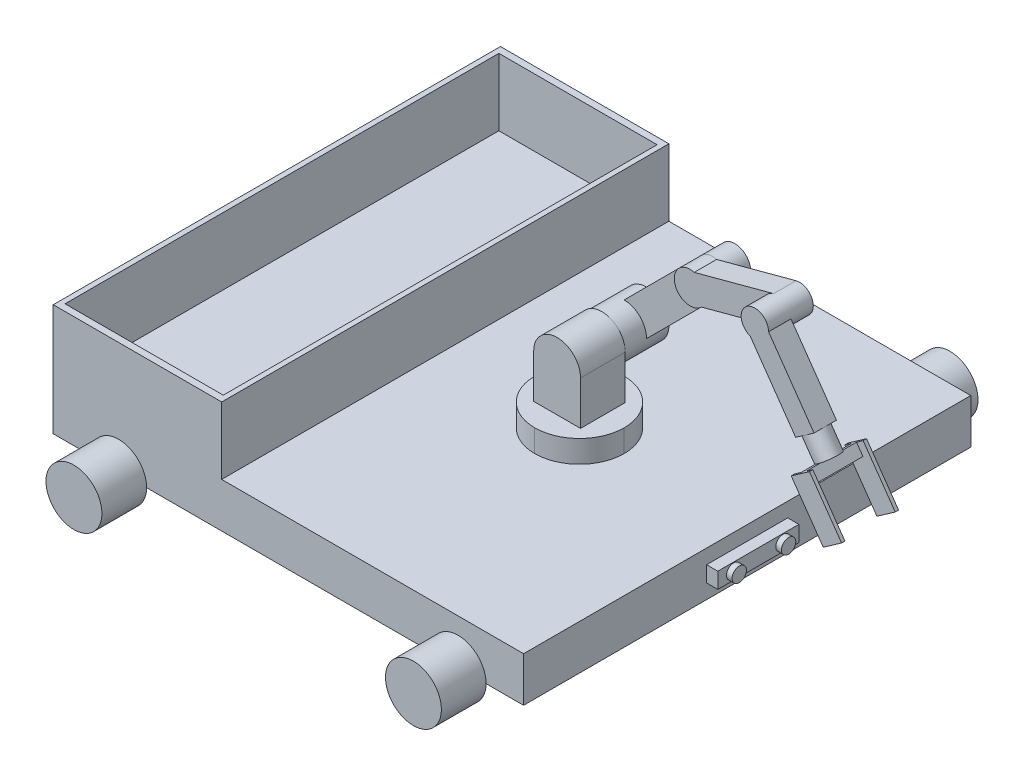
SolidWorks part; units mm, degrees
ref_plane "Front Plane" through (0, 0, 0) normal (0, 0, 1) x (1, 0, 0)
ref_plane "Top Plane" through (0, 0, 0) normal (0, 1, 0) x (1, 0, 0)
ref_plane "Right Plane" through (0, 0, 0) normal (1, 0, 0) x (0, 0, -1)
sketch "Sketch1" plane through (0, 0, 0) normal (0, 0, 1) x (1, 0, 0)
  line L0 (0, 0) -> (0, 4) construction
  line L1 (0, 0) -> (60, 0)
  line L2 (0, 4) -> (60, 4)
  line L3 (60, 4) -> (60, 0)
  line L4 (0, 4) -> (0, 0)
  line L5 (5.8519, 4) -> (5.8519, 0) construction
  line L6 (30, 4) -> (30, 0) construction
  line L7 (54.1481, 4) -> (54.1481, 0) construction
  dimension "D1" = 4
  dimension "D2" = 5.8519
extrude "Boss-Extrude1" add sketch "Sketch1" along normal blind 40
sketch "Sketch2" plane through (0, 0, 40) normal (0, 0, 1) x (1, 0, 0)
  circle A0 centre (5.8519, 0) radius 2.5
  circle A1 centre (54.1481, 0) radius 2.5
extrude "Boss-Extrude2" add sketch "Sketch2" along normal blind 4
sketch "Sketch3" plane through (0, 0, 40) normal (0, 0, 1) x (1, 0, 0)
  circle A0 centre (54.1481, 0) radius 2.5 construction
  circle A1 centre (5.8519, 0) radius 2.5 construction
  circle A2 centre (54.1481, 0) radius 2.5
  circle A3 centre (5.8519, 0) radius 2.5
extrude "Boss-Extrude3" add sketch "Sketch3" against normal blind 4 from offset 40 offset against normal yes
sketch "Sketch4" plane through (0, 0, 0) normal (0, 0, -1) x (-1, 0, 0)
  line L0 (-60, 2) -> (-30, 2) construction
  line L1 (-60, 4) -> (-60, 0) construction
  line L2 (-30, 4) -> (-30, 0) construction
  line L3 (-30, 4) -> (-45, 4) construction
  line L4 (0, 4) -> (-60, 4) construction
  line L5 (-45, 4) -> (-45, 6) construction
  line L6 (-45, 6) -> (-41, 6)
  line L7 (-41, 6) -> (-41, 4)
  line L8 (-41, 4) -> (-49, 4)
  line L9 (-49, 4) -> (-49, 6)
  line L10 (-49, 6) -> (-45, 6)
  dimension "D1" = 15
  dimension "D2" = 2
extrude "Boss-Extrude4" add sketch "Sketch4" along normal blind 4 and the other way blind 4 from offset 20 offset against normal yes
fillet "Fillet1" radius 4 4 edges at (49, 5, 24) (41, 5, 24) (41, 5, 16) (49, 5, 16)
sketch "Sketch5" plane through (0, 6, 0) normal (0, 1, 0) x (1, 0, 0)
  line L0 (45, -16) -> (45, -24) construction
  line L2 (42.906, -18) -> (47.094, -18)
  line L3 (42.906, -18) -> (42.906, -22)
  line L4 (42.906, -22) -> (47.094, -22)
  line L5 (47.094, -18) -> (47.094, -22)
  line L6 (42.906, -18) -> (47.094, -22) construction
  line L7 (42.906, -22) -> (47.094, -18) construction
  point P4 (45, -20)
  dimension "D1" = 4
extrude "Boss-Extrude5" add sketch "Sketch5" along normal blind 6
fillet "Fillet2" 2 edges at (47.094, 12, 20) (42.906, 12, 20) type full round first side face at (47.094, 9, 20) second side face at (42.906, 9, 20) middle face at (45, 12, 20)
sketch "Sketch6" plane through (0, 0, 18) normal (0, 0, -1) x (-1, 0, 0)
  line L0 (-47.094, 9.906) -> (-42.906, 9.906) construction
  circle A0 centre (-45, 9.906) radius 2
extrude "Boss-Extrude6" add sketch "Sketch6" along normal blind 2
sketch "Sketch7" plane through (0, 0, 16) normal (0, 0, -1) x (-1, 0, 0)
  line L0 (-47, 9.906) -> (-54.8995, 17.8055)
  line L1 (-45, 11.906) -> (-45, 7.906) construction
  line L2 (-54.8995, 17.8055) -> (-52.8972, 19.8077)
  line L3 (-52.8972, 19.8077) -> (-45, 11.906)
  circle A1 centre (-45, 9.906) radius 2
  arc A2 (-47, 9.906) -> (-45, 11.906) centre (-45, 9.906) ccw
  dimension "D2" = 45
  dimension "D1" = 0
extrude "Boss-Extrude7" add sketch "Sketch7" along normal blind 2
fillet "Fillet3" 2 edges at (54.8995, 17.8055, 15) (52.8972, 19.8077, 15) type full round first side face at (50.9497, 13.8557, 15) second side face at (48.9486, 15.8568, 15) middle face at (53.8984, 18.8066, 15)
sketch "Sketch8" plane through (0, 0, 16) normal (0, 0, 1) x (1, 0, 0)
  line L0 (51.8962, 18.8062) -> (53.8985, 16.8045) construction
  line L1 (53.8985, 16.8045) -> (62.1901, 19.0275)
  line L2 (53.2636, 19.1727) -> (61.5551, 21.3957)
  line L4 (61.5551, 21.3957) -> (62.1901, 19.0275)
  arc A0 (53.2636, 19.1727) -> (53.8985, 16.8045) centre (52.8974, 17.8053) ccw
  dimension "D1" = 120
  dimension "D2" = 120
extrude "Boss-Extrude8" add sketch "Sketch8" along normal blind 2
fillet "Fillet5" 2 edges at (61.5551, 21.3957, 17) (62.1901, 19.0275, 17) type full round first side face at (56.5803, 20.062, 16.8) second side face at (58.0443, 17.916, 17) middle face at (61.8726, 20.2116, 17)
sketch "Sketch9" plane through (0, 0, 18) normal (0, 0, 1) x (1, 0, 0)
  line L0 (59.4625, 19.8941) -> (61.9144, 19.8941) construction
  line L1 (61.9144, 19.8941) -> (65.9832, 14.0834)
  line L2 (60.2692, 18.7421) -> (64.3379, 12.9313)
  line L3 (64.3379, 12.9313) -> (65.9832, 14.0834)
  arc A0 (61.9144, 19.8941) -> (60.2692, 18.7421) centre (60.6885, 19.8941) ccw
  dimension "D1" = 125
  dimension "D2" = 55
extrude "Boss-Extrude9" add sketch "Sketch9" along normal blind 2
sketch "Sketch10" plane through (15.0908, -21.5519, 0) normal (0.5736, -0.8192, 0) x (-0.8192, -0.5736, 0)
  line L0 (-60.1196, -19) -> (-62.1281, -19) construction
  line L1 (-60.1196, -20) -> (-60.1196, -18) construction
  line L2 (-62.1281, -20) -> (-62.1281, -18) construction
  circle A0 centre (-61.1239, -19) radius 1
extrude "Boss-Extrude10" add sketch "Sketch10" along normal blind 2
sketch "Sketch11" plane through (16.2379, -23.1902, 0) normal (0.5736, -0.8192, 0) x (0.8192, 0.5736, 0)
  line L0 (61.1239, 20) -> (61.1239, 18) construction
  line L2 (60.8513, 21.25) -> (61.3964, 21.25)
  line L3 (60.8513, 21.25) -> (60.8513, 16.75)
  line L4 (60.8513, 16.75) -> (61.3964, 16.75)
  line L5 (61.3964, 21.25) -> (61.3964, 16.75)
  line L6 (60.8513, 21.25) -> (61.3964, 16.75) construction
  line L7 (60.8513, 16.75) -> (61.3964, 21.25) construction
  circle A0 centre (61.1239, 19) radius 1 construction
  point P6 (61.1239, 19)
  dimension "D1" = 4.5
extrude "Boss-Extrude11" add sketch "Sketch11" along normal blind 1
sketch "Sketch12" plane through (16.8115, -24.0093, 0) normal (0.5736, -0.8192, 0) x (0.8192, 0.5736, 0)
  line L0 (60.1239, 21.25) -> (62.1239, 21.25)
  line L1 (61.3964, 21.25) -> (60.8513, 21.25) construction
  line L2 (61.1239, 21.25) -> (61.1239, 22.1675) construction
  line L3 (60.1239, 21.25) -> (60.1239, 21.55)
  line L4 (60.1239, 21.55) -> (62.1239, 21.55)
  line L5 (62.1239, 21.55) -> (62.1239, 21.25)
  line L6 (60.8513, 19) -> (63.7554, 19) construction
  line L7 (60.8513, 21.25) -> (60.8513, 16.75) construction
  line L8 (60.1239, 16.45) -> (62.1239, 16.45)
  line L9 (60.1239, 16.75) -> (60.1239, 16.45)
  line L10 (60.1239, 16.75) -> (62.1239, 16.75)
  line L11 (62.1239, 16.45) -> (62.1239, 16.75)
  dimension "D1" = 1
extrude "Boss-Extrude12" add sketch "Sketch12" along normal blind 4 and the other way blind 1
sketch "Sketch14" plane through (0, 0, 0) normal (0, 0, -1) x (-1, 0, 0)
  line L0 (-17.9301, 4) -> (-17.9301, 0)
  line L1 (0, 4) -> (-60, 4) construction
  line L2 (0, 0) -> (-60, 0) construction
  line L3 (-17.9301, 0) -> (-15.6133, -10.9445)
  line L4 (-15.6133, -10.9445) -> (7.529, -7.9753)
  line L5 (7.529, -7.9753) -> (13.2054, 7.6567)
  line L6 (13.2054, 7.6567) -> (12.2964, 9.6021)
  line L7 (4.9964, 18.3108) -> (-17.9301, 4)
  line L8 (4.9964, 18.3108) -> (12.2964, 9.6021)
extrude "Cut-Extrude1" cut sketch "Sketch14" against normal blind 49 and the other way blind 14
sketch "Sketch15" plane through (0, 0, 0) normal (0, 0, -1) x (-1, 0, 0)
  circle A0 centre (-23.782, 0) radius 2.5
extrude "Boss-Extrude13" add sketch "Sketch15" along normal blind 4
sketch "Sketch16" plane through (0, 0, 40) normal (0, 0, 1) x (1, 0, 0)
  circle A0 centre (23.782, 0) radius 2.5
extrude "Boss-Extrude14" add sketch "Sketch16" along normal blind 4
sketch "Sketch17" plane through (0, 4, 0) normal (0, 1, 0) x (1, 0, 0)
  line L0 (17.9301, 0) -> (17.9301, -40) construction
  line L1 (17.9301, 0) -> (17.9301, -40)
  line L2 (32.9972, 0) -> (32.9972, -40)
  line L3 (60, 0) -> (17.9301, 0) construction
  line L4 (60, -40) -> (17.9301, -40) construction
  line L5 (32.9972, -40) -> (17.9301, -40)
  line L6 (17.9301, 0) -> (32.9972, 0)
  line L7 (17.9301, -20) -> (32.9972, -20) construction
  line L9 (18.3861, -0.5972) -> (32.5412, -0.5972)
  line L10 (18.3861, -0.5972) -> (18.3861, -39.4028)
  line L11 (18.3861, -39.4028) -> (32.5412, -39.4028)
  line L12 (32.5412, -0.5972) -> (32.5412, -39.4028)
  line L13 (18.3861, -0.5972) -> (32.5412, -39.4028) construction
  line L14 (18.3861, -39.4028) -> (32.5412, -0.5972) construction
  point P10 (25.4637, -20)
extrude "Boss-Extrude15" add sketch "Sketch17" along normal blind 6
sketch "Sketch18" plane through (60, 0, 0) normal (1, 0, 0) x (0, 0, -1)
  line L0 (-20, 4) -> (-20, 0) construction
  line L1 (-40, 0) -> (0, 0) construction
  line L2 (-20, 2) -> (-23.1645, 2) construction
  line L4 (-23.6266, 2.7066) -> (-16.3734, 2.7066)
  line L5 (-23.6266, 2.7066) -> (-23.6266, 1.2934)
  line L6 (-23.6266, 1.2934) -> (-16.3734, 1.2934)
  line L7 (-16.3734, 2.7066) -> (-16.3734, 1.2934)
  line L8 (-23.6266, 2.7066) -> (-16.3734, 1.2934) construction
  line L9 (-23.6266, 1.2934) -> (-16.3734, 2.7066) construction
extrude "Boss-Extrude16" add sketch "Sketch18" along normal blind 1
sketch "Sketch19" plane through (61, 0, 0) normal (1, 0, 0) x (0, 0, -1)
  line L0 (-23.6266, 2) -> (-16.3734, 2) construction
  line L1 (-23.6266, 2.7066) -> (-23.6266, 1.2934) construction
  line L2 (-16.3734, 1.2934) -> (-16.3734, 2.7066) construction
  line L3 (-22.2066, 2.7066) -> (-22.2066, 1.2934) construction
  line L4 (-16.3734, 2.7066) -> (-23.6266, 2.7066) construction
  line L5 (-23.6266, 1.2934) -> (-16.3734, 1.2934) construction
  line L6 (-20, 2.7066) -> (-20, 1.2934) construction
  circle A0 centre (-22.2066, 2) radius 0.6441
  circle A1 centre (-17.7934, 2) radius 0.6441
extrude "Boss-Extrude17" add sketch "Sketch19" along normal blind 0.5
sketch "Sketch20" plane through (0, 0, 0) normal (0, 0, -1) x (-1, 0, 0)
  text T0 "H.A.R.P.E.R" font "Century Gothic" height in points 5
extrude "Boss-Extrude18" add sketch "Sketch20" along normal blind 0.5
